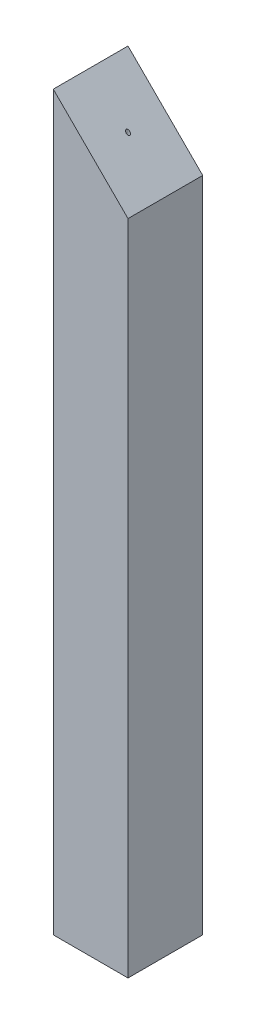
SolidWorks part; units mm, degrees
ref_plane "Front Plane" through (0, 0, 0) normal (0, 0, 1) x (1, 0, 0)
ref_plane "Top Plane" through (0, 0, 0) normal (0, 1, 0) x (1, 0, 0)
ref_plane "Right Plane" through (0, 0, 0) normal (1, 0, 0) x (0, 0, -1)
sketch "Sketch1" plane through (0, 0, 0) normal (0, 1, 0) x (1, 0, 0)
  line L1 (-12.7, 12.7) -> (12.7, 12.7)
  line L2 (-12.7, 12.7) -> (-12.7, -12.7)
  line L3 (-12.7, -12.7) -> (12.7, -12.7)
  line L4 (12.7, 12.7) -> (12.7, -12.7)
  line L5 (-12.7, 12.7) -> (12.7, -12.7) construction
  line L6 (-12.7, -12.7) -> (12.7, 12.7) construction
  point P0 (0, 0)
  dimension "D1" = 25.4
  dimension "D2" = 25.4
extrude "Boss-Extrude1" add sketch "Sketch1" along normal mid plane 248.97
hole_wizard "#0-80 Tapped Hole1" positions "Sketch2" profile "Sketch3" tap size "#0-80" standard "ANSI Inch"
sketch "Sketch2" plane through (0, -124.485, 0) normal (0, -1, 0) x (-1, 0, 0)
  point P0 (0, 0)
sketch "Sketch3" plane through (0, -124.485, 0) normal (1, 0, 0) x (0, 0, -1)
  line L0 (0, 0) -> (0, 20.3579)
  line L1 (0, 20.3579) -> (0.5956, 20)
  line L2 (0.5956, 20) -> (0.5956, 0.7683)
  line L3 (0.5956, 0.7683) -> (1.5113, 0)
  line L5 (1.5113, 0) -> (0, 0)
  line L6 (-0.5956, 0.7683) -> (-1.5113, 0) construction
  line L10 (0, 20.3579) -> (-0.5956, 20) construction
  line L11 (0, -6.35) -> (0, 107.95) construction
  dimension "Tap Drill Dia." = 1.1913
  dimension "Tap Drill Depth" = 20
  dimension "Near C'Sink Dia." = 3.0226
  dimension "Near C'Sink Angle" = 100
  dimension "Drill Angle" = 118
cosmetic thread "Hole Thread1" parameters "D1"=10, "D2"=1.524
mirror "Mirror1" about plane through (0, 0, 0) normal (0, 1, 0) of "#0-80 Tapped Hole1"
sketch "Sketch4" plane through (0, 0, 0) normal (0, 0, 1) x (1, 0, 0)
  line L0 (12.7, 124.485) -> (-12.7, 124.485)
  line L1 (-12.7, 124.485) -> (12.7, 99.085)
  line L2 (12.7, 124.485) -> (12.7, -124.485) construction
  line L3 (12.7, 99.085) -> (12.7, 124.485)
  line L4 (-12.7, 124.485) -> (-12.7, -124.485) construction
  dimension "D1" = 45
extrude "Cut-Extrude1" cut sketch "Sketch4" against normal through all both and the other way through all
